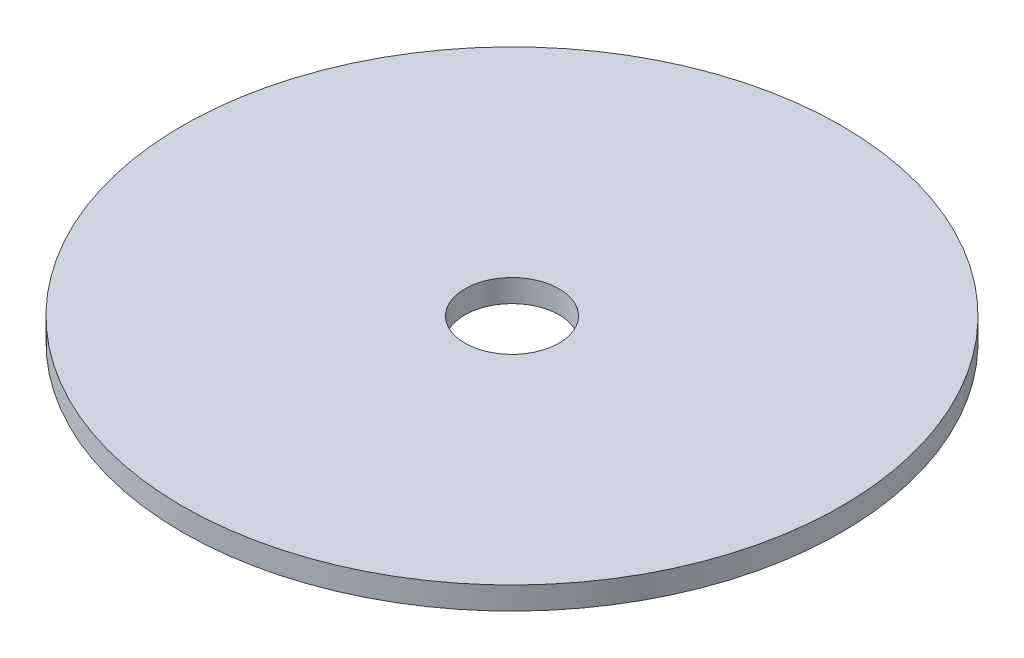
SolidWorks part; units mm, degrees
ref_plane "Front Plane" through (0, 0, 0) normal (0, 0, 1) x (1, 0, 0)
ref_plane "Top Plane" through (0, 0, 0) normal (0, 1, 0) x (1, 0, 0)
ref_plane "Right Plane" through (0, 0, 0) normal (1, 0, 0) x (0, 0, -1)
sketch "Sketch1" plane through (0, 0, 0) normal (0, 1, 0) x (1, 0, 0)
  circle A0 centre (0, 0) radius 87.5
  dimension "FLANGE_OD" = 175
extrude "Boss-Extrude1" add sketch "Sketch1" along normal blind 6
sketch "Sketch2" plane through (0, 0, 0) normal (0, 1, 0) x (1, 0, 0)
  circle A0 centre (0, 0) radius 12.5
  dimension "BORE_D" = 25
extrude "Cut-Extrude1" cut sketch "Sketch2" along normal through all
sketch "Sketch3" plane through (0, 6, 0) normal (0, 1, 0) x (1, 0, 0)
  circle A0 centre (0, 0) radius 7.9734 construction
  circle A1 centre (-7.9734, 0) radius 1.5352
  dimension "BOLT_D" = 3.0705
  dimension "BOLT_PCD" = 15.9467
extrude "Cut-Extrude2" cut sketch "Sketch3" against normal blind 3.9877 rebuild error yes
pattern_circular "CirPattern1" count 6 over 360 rebuild error yes
